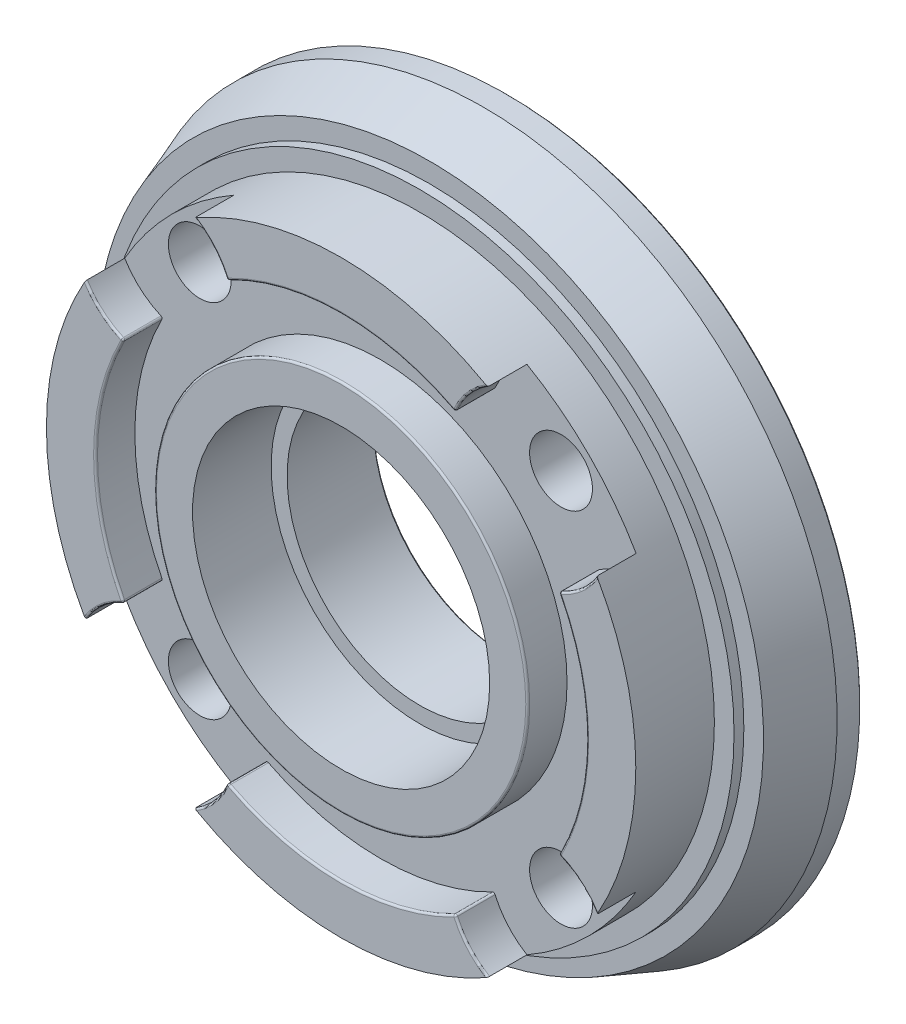
SolidWorks part; units mm, degrees
ref_plane "Front Plane" through (0, 0, 0) normal (0, 0, 1) x (1, 0, 0)
ref_plane "Top Plane" through (0, 0, 0) normal (0, 1, 0) x (1, 0, 0)
ref_plane "Right Plane" through (0, 0, 0) normal (1, 0, 0) x (0, 0, -1)
sketch "Sketch1" plane through (0, 0, 0) normal (0, 0, 1) x (1, 0, 0)
  line L0 (0, 0) -> (13.5, 0) construction
  line L1 (0, 0) -> (9.5459, 9.5459) construction
  circle A0 centre (0, 0) radius 9.5
  circle A1 centre (0, 0) radius 15
  arc A2 (-6.285, 11.9478) -> (-11.9478, 6.285) centre (0, 0) ccw construction
  arc A3 (7.4565, 13.0154) -> (5.7957, 11.0752) centre (9.5459, 9.5459) ccw
  arc A4 (13.0154, -7.4565) -> (11.0752, -5.7957) centre (9.5459, -9.5459) ccw
  arc A5 (-7.4565, -13.0154) -> (-5.7957, -11.0752) centre (-9.5459, -9.5459) ccw
  arc A6 (-13.0154, 7.4565) -> (-11.0752, 5.7957) centre (-9.5459, 9.5459) ccw
  arc A7 (-11.0752, 5.7957) -> (-11.0752, -5.7957) centre (0, 0) ccw
  arc A8 (11.9478, 6.285) -> (6.285, 11.9478) centre (0, 0) ccw construction
  arc A9 (6.285, -11.9478) -> (11.9478, -6.285) centre (0, 0) ccw construction
  arc A10 (-11.9478, -6.285) -> (-6.285, -11.9478) centre (0, 0) ccw construction
  arc A11 (5.7957, 11.0752) -> (-5.7957, 11.0752) centre (0, 0) ccw
  arc A12 (-5.7957, -11.0752) -> (5.7957, -11.0752) centre (0, 0) ccw
  arc A13 (11.0752, -5.7957) -> (11.0752, 5.7957) centre (0, 0) ccw
  arc A14 (-5.7957, 11.0752) -> (-7.4565, 13.0154) centre (-9.5459, 9.5459) ccw
  arc A15 (11.0752, 5.7957) -> (13.0154, 7.4565) centre (9.5459, 9.5459) ccw
  arc A16 (5.7957, -11.0752) -> (7.4565, -13.0154) centre (9.5459, -9.5459) ccw
  arc A17 (-11.0752, -5.7957) -> (-13.0154, -7.4565) centre (-9.5459, -9.5459) ccw
  circle A18 centre (0, 0) radius 7.5625
  point P17 (0, 0)
  dimension "D1" = 19
  dimension "D2" = 30
  dimension "D3" = 27
  dimension "D4" = 45
  dimension "D5" = 8.1
  dimension "D6" = 4
  dimension "D7" = 25
  dimension "D8" = 15.125
extrude "Boss-Extrude1" add sketch "Sketch1" along normal blind 2 contours A14 A11 A3 A1 | A15 A13 A4 A1 | A16 A12 A5 A1 | A17 A7 A6 A1 | A0 A18 region at (-9.2313, 0, 0) region at (13.2504, 0, 0) region at (0, 13.2504, 0) region at (0, -13.2504, 0) region at (-13.2504, 0, 0)
sketch "Sketch2" plane through (0, 0, 0) normal (0, 0, 1) x (1, 0, 0)
  circle A0 centre (0, 0) radius 15
extrude "Boss-Extrude2" add sketch "Sketch2" against normal blind 2
fillet "Fillet1" radius 0.1 8 edges at (-5.7957, -11.0752, 1) (5.7957, -11.0752, 1) (11.0752, -5.7957, 1) (11.0752, 5.7957, 1) (5.7957, 11.0752, 1) (-5.7957, 11.0752, 1) (-11.0752, 5.7957, 1) (-11.0752, -5.7957, 1)
fillet "Fillet2" radius 0.1 21 edges at (6.5042, 12.2199, 2) (5.7793, 11.1194, 2) (-6.5042, 12.2199, 2) (-5.7793, 11.1194, 2) (12.2199, -6.5042, 2) (11.1194, -5.7793, 2) (12.2199, 6.5042, 2) (11.1194, 5.7793, 2) (-6.5042, -12.2199, 2) (-5.7793, -11.1194, 2) (6.5042, -12.2199, 2) (5.7793, -11.1194, 2) (-12.2199, 6.5042, 2) (-11.1194, 5.7793, 2) (-12.2199, -6.5042, 2) (-11.1194, -5.7793, 2) (0, 12.5, 2) (12.5, 0, 2) (0, -12.5, 2) (9.5, 0, 2) (-12.5, 0, 2)
sketch "Sketch3" plane through (0, 0, -2) normal (0, 0, -1) x (-1, 0, 0)
  line L1 (9.1924, 9.1924) -> (-9.1924, 9.1924) construction
  line L2 (-9.1924, 9.1924) -> (-9.1924, -9.1924) construction
  line L3 (-9.1924, -9.1924) -> (9.1924, -9.1924) construction
  line L4 (9.1924, -9.1924) -> (9.1924, 9.1924) construction
  circle A0 centre (0, 0) radius 13 construction
  circle A1 centre (-9.1924, 9.1924) radius 1.6
  circle A2 centre (9.1924, 9.1924) radius 1.6
  circle A3 centre (9.1924, -9.1924) radius 1.6
  circle A4 centre (-9.1924, -9.1924) radius 1.6
  point P17 (0, 0)
  dimension "D1" = 26
  dimension "D2" = 3.2
  dimension "D3" = 4
sketch "Sketch4" plane through (0, 0, -2) normal (0, 0, -1) x (-1, 0, 0)
  circle A0 centre (0, 0) radius 16
  dimension "D1" = 32
extrude "Boss-Extrude3" add sketch "Sketch4" along normal blind 0.5
sketch "Sketch5" plane through (0, 0, -2.5) normal (0, 0, -1) x (-1, 0, 0)
  circle A0 centre (0, 0) radius 18
  dimension "D1" = 36
extrude "Boss-Extrude4" add sketch "Sketch5" along normal blind 4
extrude "Cut-Extrude2" cut sketch "Sketch3" against normal through all and the other way through all
sketch "Sketch6" plane through (0, 0, -6.5) normal (0, 0, -1) x (-1, 0, 0)
  circle A0 centre (-9.1924, 9.1924) radius 2.1
  circle A1 centre (9.1924, 9.1924) radius 2.1
  circle A2 centre (9.1924, -9.1924) radius 2.1
  circle A3 centre (-9.1924, -9.1924) radius 2.1
  point P12 (0, 0)
  dimension "D1" = 4.2
extrude "Cut-Extrude3" cut sketch "Sketch6" against normal blind 4
sketch "Sketch7" plane through (0, 0, -6.5) normal (0, 0, -1) x (-1, 0, 0)
  line L0 (0, 0) -> (0, 13) construction
  line L1 (0, 13) -> (-13, 0) construction
  line L2 (-13, 0) -> (0, -13) construction
  line L3 (0, -13) -> (13, 0) construction
  line L4 (13, 0) -> (0, 13) construction
  circle A0 centre (0, 0) radius 13 construction
  circle A1 centre (0, 13) radius 2.1
  circle A2 centre (13, 0) radius 2.1
  circle A3 centre (0, -13) radius 2.1
  circle A4 centre (-13, 0) radius 2.1
  point P17 (0, 0)
  dimension "D1" = 26
  dimension "D2" = 4.2
  dimension "D3" = 4
extrude "Cut-Extrude4" cut sketch "Sketch7" against normal blind 4
sketch "Sketch8" plane through (0, 0, 0) normal (0, 0, 1) x (1, 0, 0)
  circle A0 centre (0, 0) radius 6.75
  dimension "D1" = 13.5
extrude "Middle Cutout" cut sketch "Sketch8" against normal blind 7
chamfer "Chamfer1" distance 0.1 angle 45 2 edges at (-6.75, 0, -6.5) (-18, 0, -6.5)
sketch "Sketch9" plane through (0, 0, 0) normal (0, 0, 1) x (1, 0, 0)
  circle A0 centre (0, 0) radius 7.5625
  dimension "D1" = 15.125
extrude "Cut-Extrude6" cut sketch "Sketch9" against normal blind 2
chamfer "Chamfer2" distance 1 angle 70 1 edges at (-18, 0, -2.5) first distance on face at (-16, 0, -2.5)
equation "\"RingPinShaft\"= 5.05"
equation "\"CenterBearingOut\"=32.05"
equation "\"OutputBearingOut\"=37.05"
equation "\"RingPostIn\"=5.15"
equation "\"CamBearingOut\"=15.1"
equation "\"DiskOutputShaft\"=10.1"
equation "\"CenterShaft\"=25.2"
equation "\"Eccentricity\"=2"
equation "\"CycCamShaft\"=10.05"
equation "\"m3Thru\"=3.15"
equation "\"m3Insert\"=4.2"
equation "\"D2@Sketch7\"=\"m3Insert\""
equation "\"D1@Sketch6\"=\"m3Insert\""
